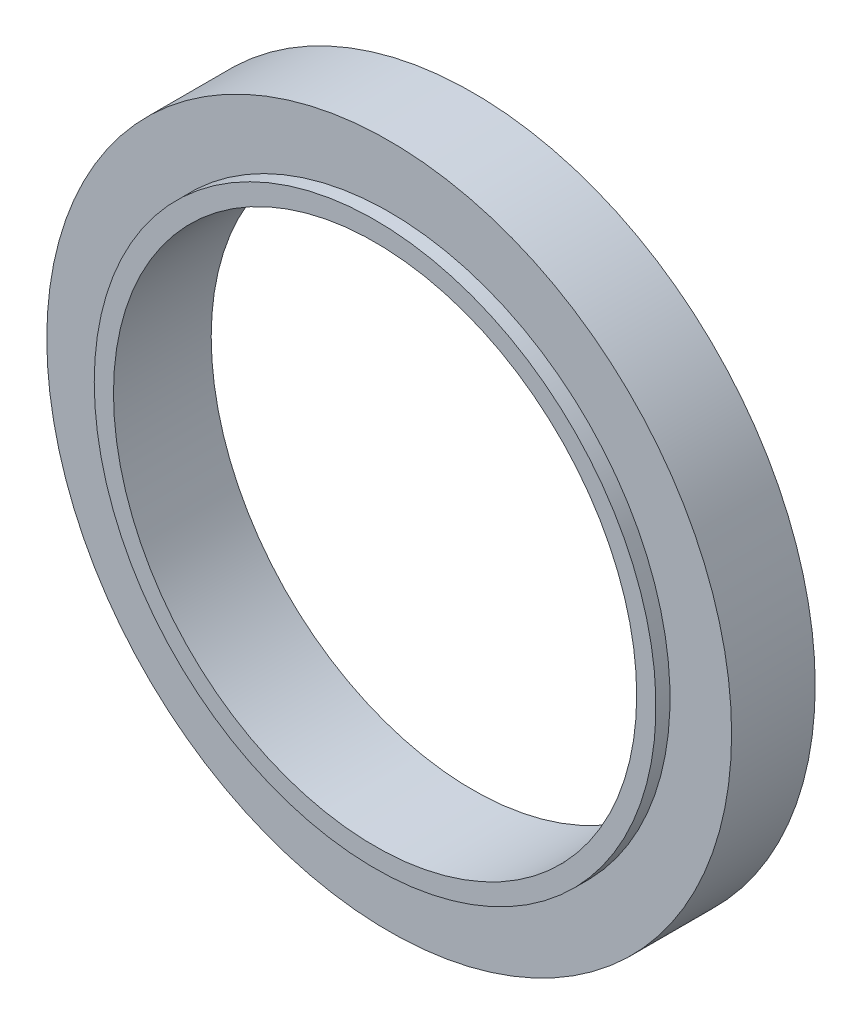
SolidWorks part; units mm, degrees
material "Cromium"
ref_plane "Front" through (0, 0, 0) normal (0, 0, 1) x (1, 0, 0)
ref_plane "Top" through (0, 0, 0) normal (0, 1, 0) x (1, 0, 0)
ref_plane "Right" through (0, 0, 0) normal (1, 0, 0) x (0, 0, -1)
sketch "Sketch1" plane through (0, 0, 0) normal (0, 0, 1) x (1, 0, 0)
  circle A0 centre (0, 0) radius 133.5
  circle A1 centre (0, 0) radius 102
  circle A2 centre (0, 0) radius 109.5
extrude "Boss-Extrude1" add sketch "Sketch1" along normal blind 38.1 contours A2 | A1
extrude "Boss-Extrude2" add sketch "Sketch1<3>" along normal blind 32.6 contours A2 | A0
sketch "Sketch1<3>" plane through (0, 0, 0) normal (0, 0, 1) x (1, 0, 0) same geometry as "Sketch1"
